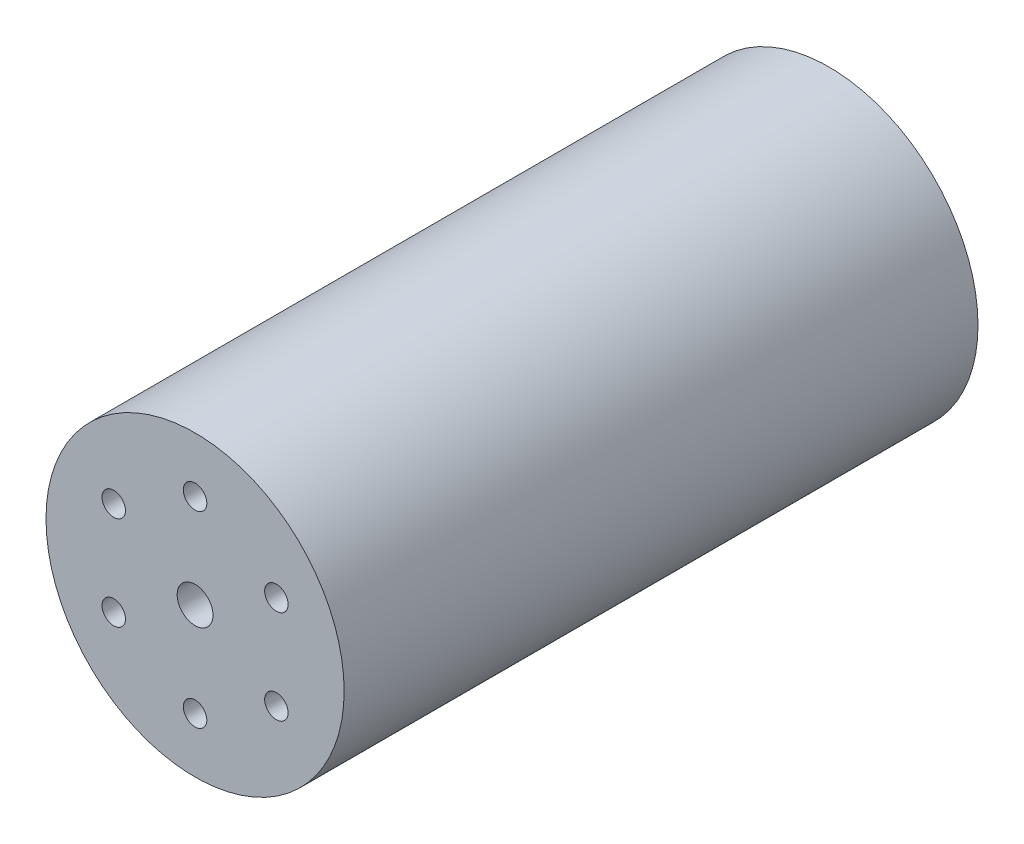
SolidWorks part; units mm, degrees
ref_plane "Front Plane" through (0, 0, 0) normal (0, 0, 1) x (1, 0, 0)
ref_plane "Top Plane" through (0, 0, 0) normal (0, 1, 0) x (1, 0, 0)
ref_plane "Right Plane" through (0, 0, 0) normal (1, 0, 0) x (0, 0, -1)
sketch "Sketch2" plane through (0, 0, 0) normal (0, 0, 1) x (1, 0, 0)
  circle A0 centre (0, 0) radius 31.75
  dimension "D1" = 63.5
extrude "Boss-Extrude1" add sketch "Sketch2" along normal blind 135 contours A0
sketch "Sketch3" plane through (0, 0, 0) normal (0, 0, -1) x (-1, 0, 0)
  circle A0 centre (0, 0) radius 3.815
  dimension "D1" = 7.63
extrude "Cut-Extrude1" cut sketch "Sketch3" against normal blind 135
sketch "Sketch5" plane through (0, 0, 0) normal (0, 0, -1) x (-1, 0, 0)
  circle A0 centre (0, 0) radius 22.225
  dimension "D1" = 44.45
extrude "Cut-Extrude2" cut sketch "Sketch5" against normal blind 30
sketch "Sketch6" plane through (0, 0, 135) normal (0, 0, 1) x (1, 0, 0)
  circle A0 centre (0, 20) radius 2.5
  circle A1 centre (17.3205, 10) radius 2.5
  circle A2 centre (17.3205, -10) radius 2.5
  circle A3 centre (0, -20) radius 2.5
  circle A4 centre (-17.3205, -10) radius 2.5
  circle A5 centre (-17.3205, 10) radius 2.5
  point P15 (0, 0)
  dimension "D1" = 20
  dimension "D2" = 5
  dimension "D3" = 6
extrude "Cut-Extrude3" cut sketch "Sketch6" against normal blind 5 contours A0
extrude "Cut-Extrude4" cut sketch "Sketch6<3>" against normal blind 5
sketch "Sketch6<3>" plane through (0, 0, 135) normal (0, 0, 1) x (1, 0, 0) same geometry as "Sketch6"
